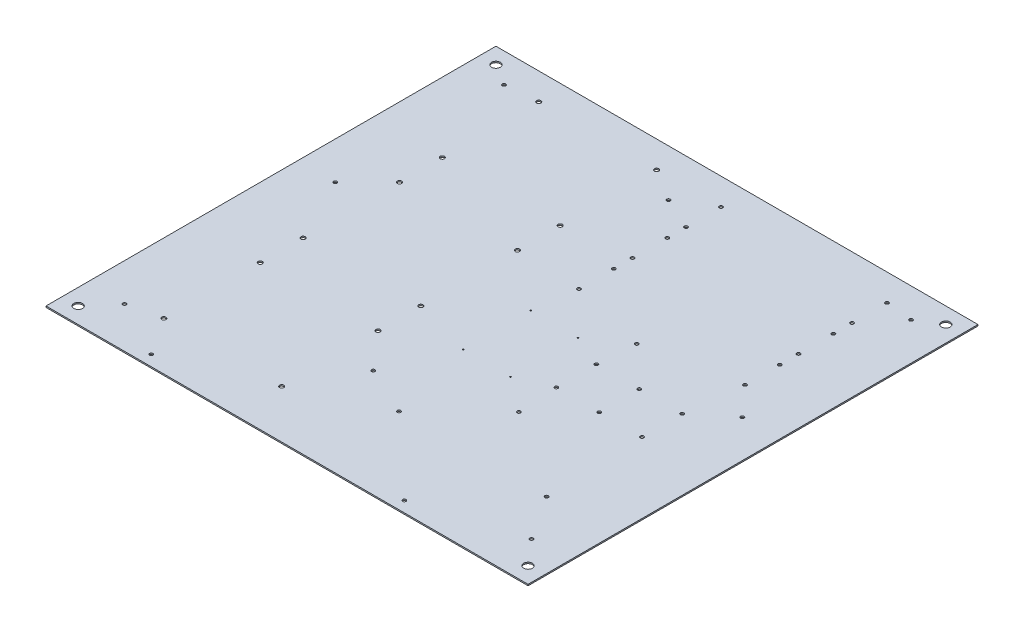
SolidWorks part; units mm, degrees
ref_plane "Front Plane" through (0, 0, 0) normal (0, 0, 1) x (1, 0, 0)
ref_plane "Top Plane" through (0, 0, 0) normal (0, 1, 0) x (1, 0, 0)
ref_plane "Right Plane" through (0, 0, 0) normal (1, 0, 0) x (0, 0, -1)
sketch "Sketch1" plane through (0, 0, 0) normal (0, 1, 0) x (1, 0, 0)
  line L1 (0, 0) -> (571.5, 0)
  line L2 (0, 0) -> (0, 533.4)
  line L3 (0, 533.4) -> (571.5, 533.4)
  line L4 (571.5, 0) -> (571.5, 533.4)
  dimension "D1" = 533.4
  dimension "D2" = 571.5
extrude "Boss-Extrude1" add sketch "Sketch1" along normal blind 1.5875
hole_wizard "#10-32 Tapped Hole1" positions "Sketch3" profile "Sketch2" tap size "#10-32" standard "ANSI Inch" end condition through all
sketch "Sketch3" plane through (0, 1.5875, 0) normal (0, 1, 0) x (1, 0, 0)
  line L0 (571.5, 533.4) -> (0, 533.4) construction
  line L1 (0, 533.4) -> (0, 0) construction
  point P0 (298.45, 501.65)
  point P2 (495.3, 501.65)
  point P4 (298.45, 460.375)
  point P6 (495.3, 460.375)
  point P21 (298.45, 438.15)
  point P22 (495.3, 438.15)
  point P23 (298.45, 396.875)
  point P24 (495.3, 396.875)
  point P25 (298.45, 374.65)
  point P26 (495.3, 374.65)
  point P27 (298.45, 333.375)
  point P28 (495.3, 333.375)
  dimension "D1" = 196.85
  dimension "D2" = 41.275
  dimension "D3" = 31.75
  dimension "D4" = 298.45
  dimension "D6" = 63.5
  dimension "D5" = 3
sketch "Sketch2" plane through (298.45, 1.5875, -501.65) normal (1, 0, 0) x (0, 0, 1)
  line L0 (0, 0) -> (0, 1.5875)
  line L1 (0, 1.5875) -> (2.0193, 1.5875)
  line L2 (2.0193, 1.5875) -> (2.0193, 0)
  line L5 (2.0193, 0) -> (0, 0)
  line L11 (0, -6.35) -> (0, 107.95) construction
  dimension "Thru Tap Drill Dia." = 4.0386
  dimension "Thru Tap Drill Depth" = 1.5875
cosmetic thread "Hole Thread1" parameters "D2"=4.826
cosmetic thread "Hole Thread2" parameters "D2"=4.826
cosmetic thread "Hole Thread3" parameters "D2"=4.826
cosmetic thread "Hole Thread4" parameters "D2"=4.826
cosmetic thread "Hole Thread17" parameters "D2"=4.826
cosmetic thread "Hole Thread18" parameters "D2"=4.826
cosmetic thread "Hole Thread19" parameters "D2"=4.826
cosmetic thread "Hole Thread20" parameters "D2"=4.826
cosmetic thread "Hole Thread21" parameters "D2"=4.826
cosmetic thread "Hole Thread22" parameters "D2"=4.826
cosmetic thread "Hole Thread23" parameters "D2"=4.826
cosmetic thread "Hole Thread24" parameters "D2"=4.826
hole_wizard "1/4-20 Tapped Hole1" positions "Sketch4" profile "Sketch5" tap size "1/4-20" standard "ANSI Inch" end condition through all
sketch "Sketch4" plane through (0, 1.5875, 0) normal (0, 1, 0) x (1, 0, 0)
  line L0 (571.5, 533.4) -> (0, 533.4) construction
  line L1 (0, 533.4) -> (0, 0) construction
  point P0 (82.55, 501.65)
  point P2 (82.55, 387.35)
  point P4 (222.25, 387.35)
  point P6 (222.25, 501.65)
  point P23 (82.55, 336.55)
  point P24 (82.55, 222.25)
  point P25 (222.25, 222.25)
  point P26 (222.25, 336.55)
  point P27 (82.55, 171.45)
  point P28 (82.55, 57.15)
  point P29 (222.25, 57.15)
  point P30 (222.25, 171.45)
  dimension "D1" = 114.3
  dimension "D2" = 139.7
  dimension "D3" = 31.75
  dimension "D4" = 82.55
  dimension "D6" = 50.8
  dimension "D5" = 3
sketch "Sketch5" plane through (82.55, 1.5875, -501.65) normal (1, 0, 0) x (0, 0, 1)
  line L0 (0, 0) -> (0, 1.5875)
  line L1 (0, 1.5875) -> (2.5527, 1.5875)
  line L2 (2.5527, 1.5875) -> (2.5527, 0)
  line L5 (2.5527, 0) -> (0, 0)
  line L11 (0, -6.35) -> (0, 107.95) construction
  dimension "Thru Tap Drill Dia." = 5.1054
  dimension "Thru Tap Drill Depth" = 1.5875
cosmetic thread "Hole Thread5" parameters "D2"=6.35
cosmetic thread "Hole Thread6" parameters "D2"=6.35
cosmetic thread "Hole Thread7" parameters "D2"=6.35
cosmetic thread "Hole Thread8" parameters "D2"=6.35
cosmetic thread "Hole Thread9" parameters "D2"=6.35
cosmetic thread "Hole Thread10" parameters "D2"=6.35
cosmetic thread "Hole Thread11" parameters "D2"=6.35
cosmetic thread "Hole Thread12" parameters "D2"=6.35
cosmetic thread "Hole Thread13" parameters "D2"=6.35
cosmetic thread "Hole Thread14" parameters "D2"=6.35
cosmetic thread "Hole Thread15" parameters "D2"=6.35
cosmetic thread "Hole Thread16" parameters "D2"=6.35
hole_wizard "M2x0.4 Tapped Hole1" positions "Sketch6" profile "Sketch7" tap size "M2x0.4" standard "ANSI Metric" end condition through all
sketch "Sketch6" plane through (0, 1.5875, 0) normal (0, 1, 0) x (1, 0, 0)
  line L0 (0, 533.4) -> (0, 0) construction
  circle A1 centre (298.45, 333.375) radius 2.0193 construction
  point P0 (292.1, 282.575)
  point P2 (348.1, 282.575)
  point P4 (292.1, 202.575)
  point P6 (348.1, 202.575)
  dimension "D1" = 80
  dimension "D2" = 56
  dimension "D3" = 292.1
  dimension "D4" = 50.8
sketch "Sketch7" plane through (292.1, 1.5875, -282.575) normal (1, 0, 0) x (0, 0, 1)
  line L0 (0, 0) -> (0, 1.5875)
  line L1 (0, 1.5875) -> (0.8, 1.5875)
  line L2 (0.8, 1.5875) -> (0.8, 0)
  line L5 (0.8, 0) -> (0, 0)
  line L11 (0, -6.35) -> (0, 107.95) construction
  dimension "Thru Tap Drill Dia." = 1.6
  dimension "Thru Tap Drill Depth" = 1.5875
cosmetic thread "Hole Thread25" parameters "D2"=2
cosmetic thread "Hole Thread26" parameters "D2"=2
cosmetic thread "Hole Thread27" parameters "D2"=2
cosmetic thread "Hole Thread28" parameters "D2"=2
hole_wizard "#10-32 Tapped Hole2" positions "Sketch8" profile "Sketch9" tap size "#10-32" standard "ANSI Inch" end condition through all
sketch "Sketch8" plane through (0, 1.5875, 0) normal (0, 1, 0) x (1, 0, 0)
  circle A4 centre (348.1, 282.575) radius 0.8 construction
  point P0 (386.2, 266.324)
  point P2 (386.2, 218.826)
  point P22 (437, 266.324)
  point P23 (437, 218.826)
  point P24 (487.8, 266.324)
  point P25 (487.8, 218.826)
  dimension "D2" = 16.251
  dimension "D3" = 38.1
  dimension "D1" = 47.498
  dimension "D5" = 50.8
  dimension "D4" = 3
sketch "Sketch9" plane through (386.2, 1.5875, -266.324) normal (1, 0, 0) x (0, 0, 1)
  line L0 (0, 0) -> (0, 1.5875)
  line L1 (0, 1.5875) -> (2.0193, 1.5875)
  line L2 (2.0193, 1.5875) -> (2.0193, 0)
  line L5 (2.0193, 0) -> (0, 0)
  line L11 (0, -6.35) -> (0, 107.95) construction
  dimension "Thru Tap Drill Dia." = 4.0386
  dimension "Thru Tap Drill Depth" = 1.5875
cosmetic thread "Hole Thread29" parameters "D2"=4.826
cosmetic thread "Hole Thread30" parameters "D2"=4.826
cosmetic thread "Hole Thread31" parameters "D2"=4.826
cosmetic thread "Hole Thread32" parameters "D2"=4.826
cosmetic thread "Hole Thread33" parameters "D2"=4.826
cosmetic thread "Hole Thread34" parameters "D2"=4.826
hole_wizard "#10-32 Tapped Hole3" positions "Sketch10" profile "Sketch11" tap size "#10-32" standard "ANSI Inch" end condition through all
sketch "Sketch10" plane through (0, 1.5875, 0) normal (0, 1, 0) x (1, 0, 0)
  line L0 (0, 533.4) -> (0, 0) construction
  circle A0 centre (348.1, 202.575) radius 0.8 construction
  point P0 (317.5, 100.975)
  point P2 (492.506, 100.975)
  dimension "D1" = 175.006
  dimension "D2" = 101.6
  dimension "D3" = 317.5
sketch "Sketch11" plane through (317.5, 1.5875, -100.975) normal (1, 0, 0) x (0, 0, 1)
  line L0 (0, 0) -> (0, 1.5875)
  line L1 (0, 1.5875) -> (2.0193, 1.5875)
  line L2 (2.0193, 1.5875) -> (2.0193, 0)
  line L5 (2.0193, 0) -> (0, 0)
  line L11 (0, -6.35) -> (0, 107.95) construction
  dimension "Thru Tap Drill Dia." = 4.0386
  dimension "Thru Tap Drill Depth" = 1.5875
cosmetic thread "Hole Thread35" parameters "D2"=4.826
cosmetic thread "Hole Thread36" parameters "D2"=4.826
hole_wizard "3/8 Clearance Hole1" positions "Sketch12" profile "Sketch13" hole size "3/8" standard "ANSI Inch" end condition through all
sketch "Sketch12" plane through (0, 1.5875, 0) normal (0, 1, 0) x (1, 0, 0)
  line L0 (0, 266.7) -> (-33.6931, 266.7)
  line L1 (0, 533.4) -> (0, 0) construction
  line L3 (285.75, 533.4) -> (285.75, 552.2627)
  line L4 (571.5, 533.4) -> (0, 533.4) construction
  point P0 (19.05, 514.35)
  point P14 (552.45, 514.35)
  point P15 (552.45, 19.05)
  point P16 (19.05, 19.05)
  dimension "D1" = 495.3
  dimension "D2" = 533.4
sketch "Sketch13" plane through (19.05, 1.5875, -514.35) normal (1, 0, 0) x (0, 0, 1)
  line L0 (0, 0) -> (0, 1.5875)
  line L1 (0, 1.5875) -> (5.1587, 1.5875)
  line L2 (5.1587, 1.5875) -> (5.1587, 0)
  line L5 (5.1587, 0) -> (0, 0)
  line L11 (0, -6.35) -> (0, 107.95) construction
  dimension "Thru Hole Dia." = 10.3175
  dimension "Thru Hole Depth" = 1.5875
sketch "Sketch16" plane through (0, 1.5875, 0) normal (0, 1, 0) x (1, 0, 0)
  line L0 (527.05, 52.25) -> (527.05, 44.75)
  line L1 (527.05, 502.25) -> (527.05, 494.75)
  line L2 (527.05, 302.25) -> (527.05, 294.75)
  line L7 (47.7, 3.75) -> (47.7, 0)
  line L8 (47.7, 0) -> (55.0862, 0)
  line L9 (55.0862, 0) -> (55.0862, 533.4)
  line L10 (55.0862, 533.4) -> (33.8137, 533.4)
  line L11 (33.8137, 533.4) -> (33.8137, 0)
  line L12 (33.8137, 0) -> (41.2, 0)
  line L13 (41.2, 0) -> (41.2, 3.75)
  line L14 (47.7, 3.75) -> (47.7, 0)
  line L15 (47.7, 0) -> (55.0862, 0)
  line L16 (55.0862, 0) -> (55.0862, 533.4)
  line L17 (55.0862, 533.4) -> (33.8137, 533.4)
  line L18 (33.8137, 533.4) -> (33.8137, 0)
  line L19 (33.8137, 0) -> (41.2, 0)
  line L20 (41.2, 0) -> (41.2, 3.75)
  line L21 (530.3, 3.75) -> (530.3, 0)
  line L22 (530.3, 0) -> (537.6863, 0)
  line L23 (537.6863, 0) -> (537.6863, 533.4)
  line L24 (537.6863, 533.4) -> (516.4138, 533.4)
  line L25 (516.4138, 533.4) -> (516.4138, 0)
  line L26 (516.4138, 0) -> (523.8, 0)
  line L27 (523.8, 0) -> (523.8, 3.75)
  line L28 (530.3, 3.75) -> (530.3, 0)
  line L29 (530.3, 0) -> (537.6863, 0)
  line L30 (537.6863, 0) -> (537.6863, 533.4)
  line L31 (537.6863, 533.4) -> (516.4138, 533.4)
  line L32 (516.4138, 533.4) -> (516.4138, 0)
  line L33 (516.4138, 0) -> (523.8, 0)
  line L34 (523.8, 0) -> (523.8, 3.75)
  line L35 (510.6, 15.95) -> (514.35, 15.95)
  line L36 (514.35, 15.95) -> (514.35, 23.3362)
  line L37 (514.35, 23.3362) -> (57.15, 23.3362)
  line L38 (57.15, 23.3362) -> (57.15, 2.0637)
  line L39 (57.15, 2.0637) -> (514.35, 2.0637)
  line L40 (514.35, 2.0637) -> (514.35, 9.45)
  line L41 (514.35, 9.45) -> (510.6, 9.45)
  line L42 (510.6, 15.95) -> (514.35, 15.95)
  line L43 (514.35, 15.95) -> (514.35, 23.3362)
  line L44 (514.35, 23.3362) -> (57.15, 23.3362)
  line L45 (57.15, 23.3362) -> (57.15, 2.0637)
  line L46 (57.15, 2.0637) -> (514.35, 2.0637)
  line L47 (514.35, 2.0637) -> (514.35, 9.45)
  line L48 (514.35, 9.45) -> (510.6, 9.45)
  line L49 (510.6, 174.7) -> (514.35, 174.7)
  line L50 (514.35, 174.7) -> (514.35, 182.0862)
  line L51 (514.35, 182.0862) -> (273.05, 182.0862)
  line L52 (273.05, 182.0862) -> (273.05, 160.8137)
  line L53 (273.05, 160.8137) -> (514.35, 160.8137)
  line L54 (514.35, 160.8137) -> (514.35, 168.2)
  line L55 (514.35, 168.2) -> (510.6, 168.2)
  line L56 (510.6, 174.7) -> (514.35, 174.7)
  line L57 (514.35, 174.7) -> (514.35, 182.0862)
  line L58 (514.35, 182.0862) -> (273.05, 182.0862)
  line L59 (273.05, 182.0862) -> (273.05, 160.8137)
  line L60 (273.05, 160.8137) -> (514.35, 160.8137)
  line L61 (514.35, 160.8137) -> (514.35, 168.2)
  line L62 (514.35, 168.2) -> (510.6, 168.2)
  line L63 (44.45, 494.75) -> (44.45, 502.25)
  line L64 (44.45, 44.75) -> (44.45, 52.25)
  line L65 (44.45, 294.75) -> (44.45, 302.25)
  line L70 (510.6, 314.4) -> (514.35, 314.4)
  line L71 (514.35, 314.4) -> (514.35, 321.7862)
  line L72 (514.35, 321.7862) -> (273.05, 321.7862)
  line L73 (273.05, 321.7862) -> (273.05, 300.5137)
  line L74 (273.05, 300.5137) -> (514.35, 300.5137)
  line L75 (514.35, 300.5137) -> (514.35, 307.9)
  line L76 (514.35, 307.9) -> (510.6, 307.9)
  line L77 (510.6, 314.4) -> (514.35, 314.4)
  line L78 (514.35, 314.4) -> (514.35, 321.7862)
  line L79 (514.35, 321.7862) -> (273.05, 321.7862)
  line L80 (273.05, 321.7862) -> (273.05, 300.5137)
  line L81 (273.05, 300.5137) -> (514.35, 300.5137)
  line L82 (514.35, 300.5137) -> (514.35, 307.9)
  line L83 (514.35, 307.9) -> (510.6, 307.9)
  line L84 (263.6, 29.15) -> (263.6, 25.4)
  line L85 (263.6, 25.4) -> (270.9863, 25.4)
  line L86 (270.9863, 25.4) -> (270.9863, 533.4)
  line L87 (270.9863, 533.4) -> (249.7138, 533.4)
  line L88 (249.7138, 533.4) -> (249.7138, 25.4)
  line L89 (249.7138, 25.4) -> (257.1, 25.4)
  line L90 (257.1, 25.4) -> (257.1, 29.15)
  line L91 (263.6, 29.15) -> (263.6, 25.4)
  line L92 (263.6, 25.4) -> (270.9863, 25.4)
  line L93 (270.9863, 25.4) -> (270.9863, 533.4)
  line L94 (270.9863, 533.4) -> (249.7138, 533.4)
  line L95 (249.7138, 533.4) -> (249.7138, 25.4)
  line L96 (249.7138, 25.4) -> (257.1, 25.4)
  line L97 (257.1, 25.4) -> (257.1, 29.15)
  arc A1 (47.7, 3.75) -> (41.2, 3.75) centre (44.45, 3.75) ccw
  arc A2 (47.7, 3.75) -> (41.2, 3.75) centre (44.45, 3.75) ccw
  arc A3 (530.3, 3.75) -> (523.8, 3.75) centre (527.05, 3.75) ccw
  arc A4 (530.3, 3.75) -> (523.8, 3.75) centre (527.05, 3.75) ccw
  arc A5 (510.6, 15.95) -> (510.6, 9.45) centre (510.6, 12.7) ccw
  arc A6 (510.6, 15.95) -> (510.6, 9.45) centre (510.6, 12.7) ccw
  arc A7 (510.6, 174.7) -> (510.6, 168.2) centre (510.6, 171.45) ccw
  arc A8 (510.6, 174.7) -> (510.6, 168.2) centre (510.6, 171.45) ccw
  arc A10 (510.6, 314.4) -> (510.6, 307.9) centre (510.6, 311.15) ccw
  arc A11 (510.6, 314.4) -> (510.6, 307.9) centre (510.6, 311.15) ccw
  arc A12 (263.6, 29.15) -> (257.1, 29.15) centre (260.35, 29.15) ccw
  arc A13 (263.6, 29.15) -> (257.1, 29.15) centre (260.35, 29.15) ccw
  point P0 (44.45, 498.5)
  point P49 (44.45, 48.5)
  point P68 (44.45, 298.5)
  point P73 (527.05, 48.5)
  point P78 (527.05, 498.5)
  point P83 (527.05, 298.5)
  point P84 (260.35, 127.65)
  point P85 (260.35, 477.65)
  point P87 (389.1, 311.15)
  point P89 (389.1, 171.45)
  point P91 (412.1, 12.7)
  point P93 (112.1, 12.7)
  dimension "D1" = 0
  dimension "D2" = 0
  dimension "D3" = 0
  dimension "D4" = 0
  dimension "D5" = 0
  dimension "D6" = 0
hole_wizard "#10-32 Tapped Hole4" positions "Sketch16" profile "Sketch17" tap size "#10-32" standard "ANSI Inch" end condition up to next
sketch "Sketch17" plane through (44.45, 1.5875, -498.5) normal (1, 0, 0) x (0, 0, 1)
  line L0 (0, 0) -> (0, 1.5875)
  line L1 (0, 1.5875) -> (2.0193, 1.5875)
  line L2 (2.0193, 1.5875) -> (2.0193, 0)
  line L5 (2.0193, 0) -> (0, 0)
  line L11 (0, -6.35) -> (0, 107.95) construction
  dimension "Thru Tap Drill Dia." = 4.0386
  dimension "Thru Tap Drill Depth" = 1.5875
cosmetic thread "Hole Thread37" parameters "D2"=4.826
cosmetic thread "Hole Thread38" parameters "D2"=4.826
cosmetic thread "Hole Thread39" parameters "D2"=4.826
cosmetic thread "Hole Thread40" parameters "D2"=4.826
cosmetic thread "Hole Thread41" parameters "D2"=4.826
cosmetic thread "Hole Thread42" parameters "D2"=4.826
cosmetic thread "Hole Thread43" parameters "D2"=4.826
cosmetic thread "Hole Thread44" parameters "D2"=4.826
cosmetic thread "Hole Thread45" parameters "D2"=4.826
cosmetic thread "Hole Thread46" parameters "D2"=4.826
cosmetic thread "Hole Thread47" parameters "D2"=4.826
cosmetic thread "Hole Thread48" parameters "D2"=4.826
